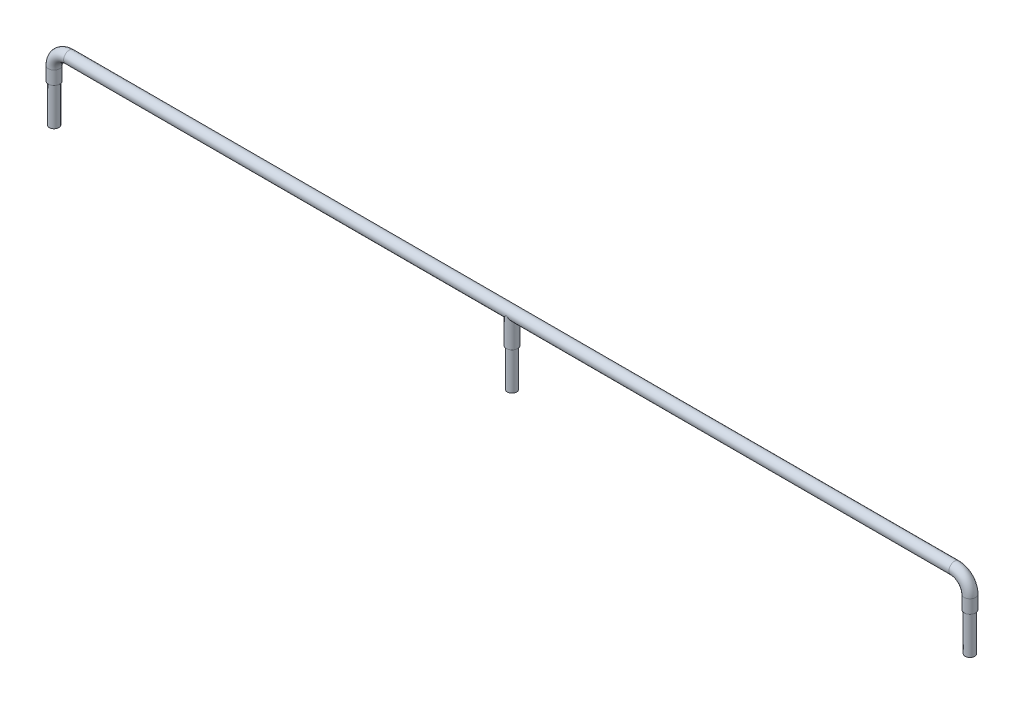
SolidWorks part; units mm, degrees
ref_plane "前视基准面" through (0, 0, 0) normal (0, 0, 1) x (1, 0, 0)
ref_plane "上视基准面" through (0, 0, 0) normal (0, 1, 0) x (1, 0, 0)
ref_plane "右视基准面" through (0, 0, 0) normal (1, 0, 0) x (0, 0, -1)
sketch "草图1" plane through (0, 0, 0) normal (0, 0, 1) x (1, 0, 0)
  line L0 (-2400, 0) -> (-2400, 270)
  line L1 (-2320, 350) -> (2320, 350)
  line L2 (2400, 270) -> (2400, 0)
  line L3 (0, 350) -> (0, 0) construction
  line L4 (-2400, 0) -> (0, 0) construction
  line L5 (0, 0) -> (2400, 0) construction
  arc A0 (2320, 350) -> (2400, 270) centre (2320, 270) cw
  arc A1 (-2400, 270) -> (-2320, 350) centre (-2320, 270) cw
  point P7 (-2252.0555, 0)
  point P10 (2400, 350)
  point P13 (-2400, 350)
  dimension "D3" = 80
  dimension "D1" = 350
  dimension "D2" = 4800
sweep "扫描-薄件1" add path "草图1" circular profile diameter 60 parameters "D1"=10, "D3"=60
sketch "草图78" plane through (0, 0, 0) normal (0, -1, 0) x (1, 0, 0)
  circle A0 centre (0, 0) radius 30
  circle A1 centre (0, 0) radius 20
  dimension "D1" = 60
  dimension "D2" = 40
extrude "凸台-拉伸1" add sketch "草图78" against normal up to surface (320 mm away) up to face at (2320, 320, 0)
sketch "草图79" plane through (0, 0, 0) normal (0, -1, 0) x (1, 0, 0)
  circle A0 centre (-2400, 0) radius 25
  circle A1 centre (-2400, 0) radius 30
  circle A2 centre (0, 0) radius 25
  circle A3 centre (0, 0) radius 30
  circle A4 centre (2400, 0) radius 25
  circle A5 centre (2400, 0) radius 30
  circle A6 centre (-2400, 0) radius 30 construction
  circle A7 centre (2400, 0) radius 30 construction
  arc A8 (0, -30) -> (0, 30) centre (0, 0) ccw construction
  dimension "D1" = 50
extrude "切除-拉伸1" cut sketch "草图79" against normal blind 200
